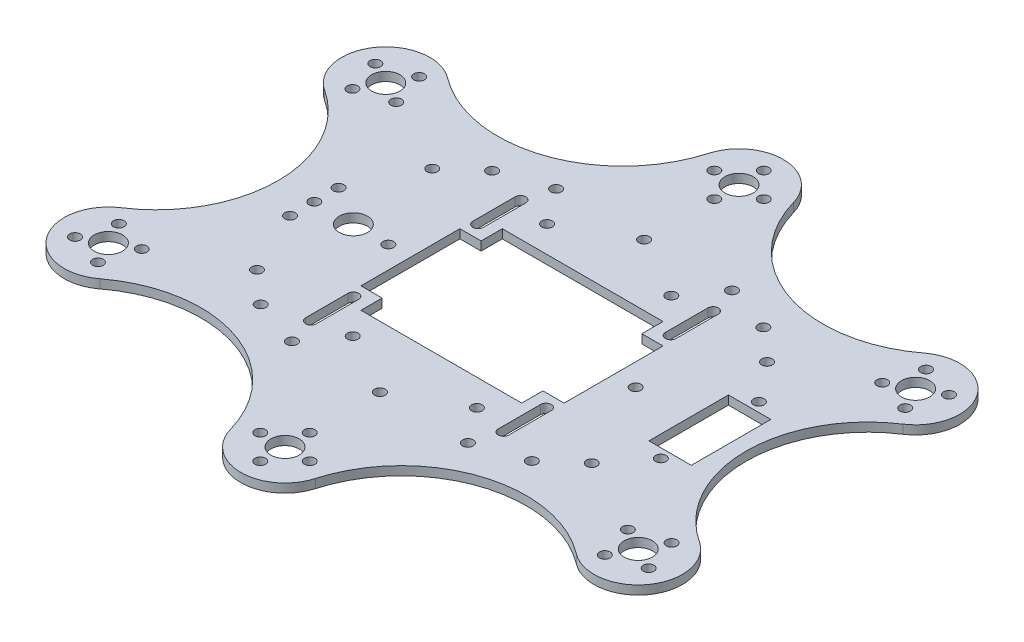
SolidWorks part; units mm, degrees
ref_plane "Front Plane" through (0, 0, 0) normal (0, 0, 1) x (1, 0, 0)
ref_plane "Top Plane" through (0, 0, 0) normal (0, 1, 0) x (1, 0, 0)
ref_plane "Right Plane" through (0, 0, 0) normal (1, 0, 0) x (0, 0, -1)
sketch "Sketch1" plane through (0, 0, 0) normal (0, 1, 0) x (1, 0, 0)
  line L0 (0, 79.6556) -> (0, -85.1852) construction
  line L2 (-28.75, -20) -> (-28.75, -17.65)
  line L4 (28.75, -20) -> (28.75, -17.65)
  line L5 (-28.75, -20) -> (28.75, 20) construction
  line L6 (-28.75, 20) -> (28.75, -20) construction
  line L7 (-91.2557, 0) -> (90.8672, 0) construction
  line L8 (0, 0) -> (74.9766, 39.25) construction
  line L9 (27.25, 17.65) -> (27.25, 29.65) construction
  line L10 (25.75, 17.65) -> (25.75, 29.65)
  line L11 (28.75, 17.65) -> (28.75, 29.65)
  line L12 (-22.75, 20) -> (-22.75, 14)
  line L14 (28.75, 20) -> (28.75, 17.65)
  line L15 (28.75, 14) -> (22.75, 14)
  line L16 (22.75, 20) -> (22.75, 14)
  line L17 (-28.75, 14) -> (-22.75, 14)
  line L18 (-28.75, 20) -> (-28.75, 17.65)
  line L20 (-27.25, 17.65) -> (-27.25, 29.65) construction
  line L21 (-25.75, 17.65) -> (-25.75, 29.65)
  line L22 (-28.75, 17.65) -> (-28.75, 29.65)
  line L24 (-28.75, -20) -> (-28.75, -17.65)
  line L25 (-28.75, -14) -> (-22.75, -14)
  line L26 (22.75, -20) -> (22.75, -14)
  line L27 (28.75, -14) -> (22.75, -14)
  line L28 (28.75, -20) -> (28.75, -17.65)
  line L30 (-22.75, -20) -> (-22.75, -14)
  line L31 (-74.9766, -39.25) -> (74.9766, 39.25) construction
  line L32 (-27.25, -17.65) -> (-27.25, -29.65) construction
  line L33 (-25.75, -17.65) -> (-25.75, -29.65)
  line L34 (-28.75, -17.65) -> (-28.75, -29.65)
  line L35 (27.25, -17.65) -> (27.25, -29.65) construction
  line L36 (25.75, -17.65) -> (25.75, -29.65)
  line L37 (28.75, -17.65) -> (28.75, -29.65)
  line L38 (66.25, 79.6556) -> (66.25, -85.1852) construction
  line L39 (-66.25, 79.6556) -> (-66.25, -85.1852) construction
  line L40 (-91.2557, 42) -> (90.8672, 42) construction
  line L41 (-91.2557, -42) -> (90.8672, -42) construction
  line L42 (-22.75, 20) -> (22.75, 20)
  line L43 (-28.75, 17.65) -> (-28.75, 20)
  line L44 (28.75, 17.65) -> (28.75, 20)
  line L45 (28.75, -14) -> (28.75, 14)
  line L46 (-22.75, -20) -> (22.75, -20)
  line L47 (-22.75, -20) -> (22.75, -20)
  line L48 (-28.75, -14) -> (-28.75, 14)
  line L49 (-74.9766, 39.25) -> (74.9766, -39.25) construction
  line L50 (0, 0) -> (-46.0262, -77.3558) construction
  line L52 (50, -11.25) -> (62, -11.25)
  line L53 (50, -11.25) -> (50, 11.25)
  line L54 (50, 11.25) -> (62, 11.25)
  line L55 (62, -11.25) -> (62, 11.25)
  line L56 (50, -11.25) -> (62, 11.25) construction
  line L57 (50, 11.25) -> (62, -11.25) construction
  circle A0 centre (0, 64.25) radius 4
  arc A1 (12.0221, 67.6732) -> (-12.0221, 67.6732) centre (0, 64.25) ccw
  circle A2 centre (0, 64.25) radius 7 construction
  circle A3 centre (-7, 64.25) radius 1.5
  circle A4 centre (0, 57.25) radius 1.5
  circle A5 centre (7, 64.25) radius 1.5
  circle A6 centre (0, 71.25) radius 1.5
  circle A7 centre (0, 37.375) radius 1.5
  circle A8 centre (17.575, 27.5) radius 1.5
  circle A9 centre (24.9, 37.375) radius 1.5
  circle A10 centre (38.375, 32.75) radius 1.5
  circle A11 centre (47.375, 24.8006) radius 1.5
  circle A12 centre (74.9766, 39.25) radius 4
  arc A13 (81.8194, 28.7893) -> (67.4147, 49.2033) centre (74.9766, 39.25) ccw
  circle A14 centre (74.9766, 39.25) radius 7 construction
  circle A15 centre (68.775, 36.0035) radius 1.5
  circle A16 centre (71.7301, 45.4516) radius 1.5
  circle A17 centre (81.1782, 42.4965) radius 1.5
  circle A18 centre (78.2231, 33.0484) radius 1.5
  arc A19 (25.75, 17.65) -> (28.75, 17.65) centre (27.25, 17.65) ccw
  arc A20 (28.75, 29.65) -> (25.75, 29.65) centre (27.25, 29.65) ccw
  circle A21 centre (35, 0) radius 1.5
  circle A22 centre (-35, 0) radius 1.5
  circle A23 centre (-47.375, 24.8006) radius 1.5
  circle A24 centre (-38.375, 32.75) radius 1.5
  circle A25 centre (-17.575, 27.5) radius 1.5
  arc A26 (-25.75, 17.65) -> (-28.75, 17.65) centre (-27.25, 17.65) cw
  arc A27 (-28.75, 29.65) -> (-25.75, 29.65) centre (-27.25, 29.65) cw
  circle A28 centre (-24.9, 37.375) radius 1.5
  circle A29 centre (-74.9766, 39.25) radius 7 construction
  circle A30 centre (-78.2231, 33.0484) radius 1.5
  circle A31 centre (-81.1782, 42.4965) radius 1.5
  circle A32 centre (-71.7301, 45.4516) radius 1.5
  circle A33 centre (-68.775, 36.0035) radius 1.5
  arc A34 (-81.8194, 28.7893) -> (-67.4147, 49.2033) centre (-74.9766, 39.25) cw
  circle A35 centre (-74.9766, 39.25) radius 4
  circle A36 centre (-24.9, -37.375) radius 1.5
  circle A37 centre (-17.575, -27.5) radius 1.5
  circle A38 centre (-38.375, -32.75) radius 1.5
  circle A39 centre (-47.375, -24.8006) radius 1.5
  circle A40 centre (47.375, -24.8006) radius 1.5
  circle A41 centre (38.375, -32.75) radius 1.5
  circle A42 centre (24.9, -37.375) radius 1.5
  circle A43 centre (17.575, -27.5) radius 1.5
  circle A44 centre (0, -37.375) radius 1.5
  arc A45 (-25.75, -17.65) -> (-28.75, -17.65) centre (-27.25, -17.65) ccw
  arc A46 (-28.75, -29.65) -> (-25.75, -29.65) centre (-27.25, -29.65) ccw
  arc A47 (25.75, -17.65) -> (28.75, -17.65) centre (27.25, -17.65) cw
  arc A48 (28.75, -29.65) -> (25.75, -29.65) centre (27.25, -29.65) cw
  circle A49 centre (0, -64.25) radius 7 construction
  circle A50 centre (0, -71.25) radius 1.5
  circle A51 centre (7, -64.25) radius 1.5
  circle A52 centre (0, -57.25) radius 1.5
  circle A53 centre (-7, -64.25) radius 1.5
  arc A54 (12.0221, -67.6732) -> (-12.0221, -67.6732) centre (0, -64.25) cw
  circle A55 centre (0, -64.25) radius 4
  circle A56 centre (74.9766, -39.25) radius 7 construction
  circle A57 centre (78.2231, -33.0484) radius 1.5
  circle A58 centre (81.1782, -42.4965) radius 1.5
  circle A59 centre (71.7301, -45.4516) radius 1.5
  circle A60 centre (68.775, -36.0035) radius 1.5
  arc A61 (81.8194, -28.7893) -> (67.4147, -49.2033) centre (74.9766, -39.25) cw
  circle A62 centre (74.9766, -39.25) radius 4
  circle A63 centre (-74.9766, -39.25) radius 7 construction
  circle A64 centre (-74.9766, -39.25) radius 4
  arc A65 (-81.8194, -28.7893) -> (-67.4147, -49.2033) centre (-74.9766, -39.25) ccw
  circle A66 centre (-68.775, -36.0035) radius 1.5
  circle A67 centre (-71.7301, -45.4516) radius 1.5
  circle A68 centre (-81.1782, -42.4965) radius 1.5
  circle A69 centre (-78.2231, -33.0484) radius 1.5
  arc A70 (-81.8194, -28.7893) -> (-81.8194, 28.7893) centre (-100.6518, 0) ccw
  arc A71 (81.8194, -28.7893) -> (81.8194, 28.7893) centre (100.6518, 0) cw
  arc A72 (-12.0221, -67.6732) -> (-67.4147, -49.2033) centre (-46.0262, -77.3558) ccw
  arc A73 (-12.0221, 67.6732) -> (-67.4147, 49.2033) centre (-46.0262, 77.3558) cw
  arc A74 (12.0221, -67.6732) -> (67.4147, -49.2033) centre (46.0262, -77.3558) cw
  arc A75 (12.0221, 67.6732) -> (67.4147, 49.2033) centre (46.0262, 77.3558) ccw
  circle A76 centre (56, 13.875) radius 1.5
  circle A77 centre (56, -13.875) radius 1.5
  circle A78 centre (-44.9, 0) radius 4
  circle A79 centre (-55.95, 0) radius 1.5
  circle A80 centre (-55.95, 6.875) radius 1.5
  circle A81 centre (-55.95, -6.875) radius 1.5
  point P0 (0, 0)
  point P25 (0, 64.25)
  point P42 (27.25, 23.65)
  point P49 (74.9766, 39.25)
  point P72 (-27.25, 23.65)
  point P89 (56, 0)
  point P91 (-74.9766, 39.25)
  point P121 (-27.25, -23.65)
  point P128 (27.25, -23.65)
  point P145 (0, -64.25)
  point P158 (74.9766, -39.25)
  point P171 (-74.9766, -39.25)
  point P210 (0, 0)
  dimension "D3" = 25
  dimension "D4" = 8
  dimension "D5" = 14
  dimension "D6" = 3
  dimension "D11" = 3.65
  dimension "D1" = 40
  dimension "D2" = 57.5
  dimension "D9" = 12
  dimension "D10" = 3
  dimension "D12" = 40
  dimension "D13" = 74.75
  dimension "D14" = 24.9
  dimension "D15" = 137.55
  dimension "D16" = 28
  dimension "D17" = 35.15
  dimension "D18" = 70
  dimension "D19" = 94.75
  dimension "D20" = 78.5
  dimension "D21" = 76.75
  dimension "D22" = 65.5
  dimension "D23" = 128.5
  dimension "D24" = 132.5
  dimension "D25" = 84
  dimension "D26" = 55
  dimension "D27" = 12
  dimension "D28" = 22.5
  dimension "D29" = 21.25
  dimension "D30" = 27.75
  dimension "D31" = 13.75
  dimension "D32" = 11.05
  dimension "D33" = 9.9
  dimension "D7" = 4
  dimension "D8" = 4
extrude "Boss-Extrude1" add sketch "Sketch1" along normal blind 2.5 contours A75 A1 A73 A34 A70 A65 A72 A54 A74 A61 A71 A13 A77 A76 A69 A68 A67 A66 A64 A60 A58 A55 A52 A50 A46 L34 L2 A45 L33 A43 A41 A35 A32 region at (34.1064, 0, -41.6074)
